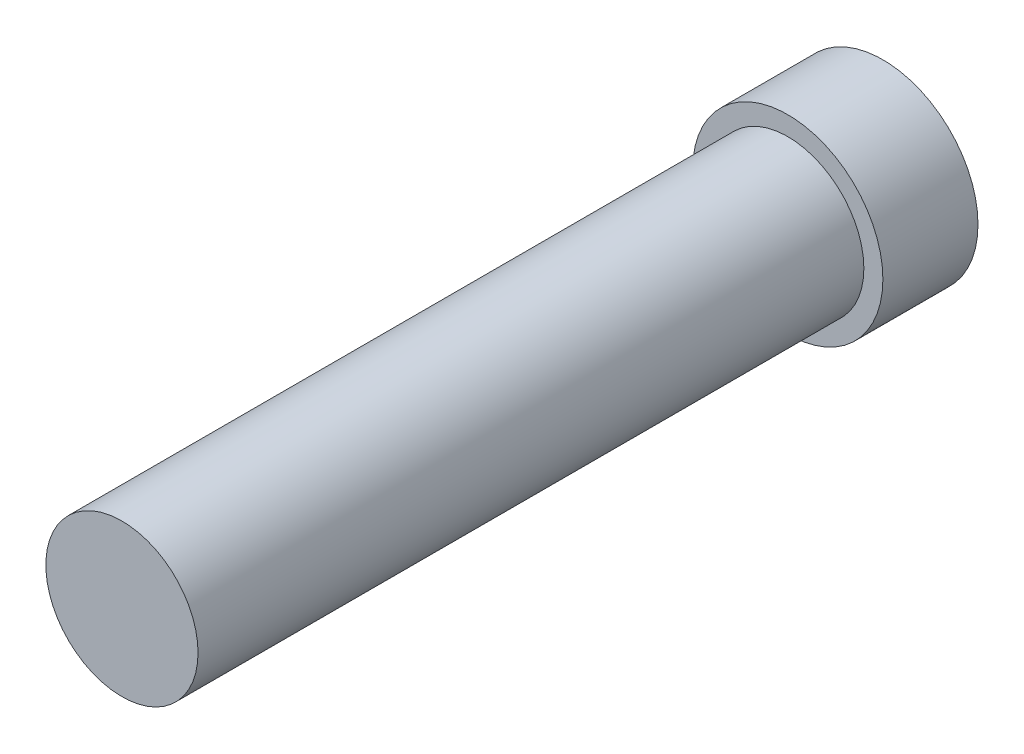
SolidWorks part; units mm, degrees
ref_plane "Front Plane" through (0, 0, 0) normal (0, 0, 1) x (1, 0, 0)
ref_plane "Top Plane" through (0, 0, 0) normal (0, 1, 0) x (1, 0, 0)
ref_plane "Right Plane" through (0, 0, 0) normal (1, 0, 0) x (0, 0, -1)
sketch "Sketch1" plane through (0, 0, 0) normal (0, 0, 1) x (1, 0, 0)
  circle A0 centre (0, 0) radius 4
  circle A1 centre (0, 0) radius 5
  dimension "D1" = 10
  dimension "D2" = 8
extrude "Boss-Extrude1" add sketch "Sketch1" along normal blind 40 contours A0
extrude "Boss-Extrude2" add sketch "Sketch1<5>" along normal blind 5
sketch "Sketch1<5>" plane through (0, 0, 0) normal (0, 0, 1) x (1, 0, 0) same geometry as "Sketch1"
sketch "Sketch2" plane through (0, 0, 0) normal (0, 0, -1) x (-1, 0, 0)
  line L1 (-1.6008, 3.9899) -> (-4.2557, 0.6086)
  line L2 (-4.2557, 0.6086) -> (-2.6549, -3.3812)
  line L3 (-2.6549, -3.3812) -> (1.6008, -3.9899)
  line L4 (1.6008, -3.9899) -> (4.2557, -0.6086)
  line L5 (4.2557, -0.6086) -> (2.6549, 3.3812)
  line L6 (2.6549, 3.3812) -> (-1.6008, 3.9899)
  circle A0 centre (0, 0) radius 3.7231 construction
extrude "Cut-Extrude3" cut sketch "Sketch2" against normal blind 1
extrude "Cut-Extrude4" cut sketch "Sketch2<2>" against normal blind 2
sketch "Sketch2<2>" plane through (0, 0, 0) normal (0, 0, -1) x (-1, 0, 0) same geometry as "Sketch2"
